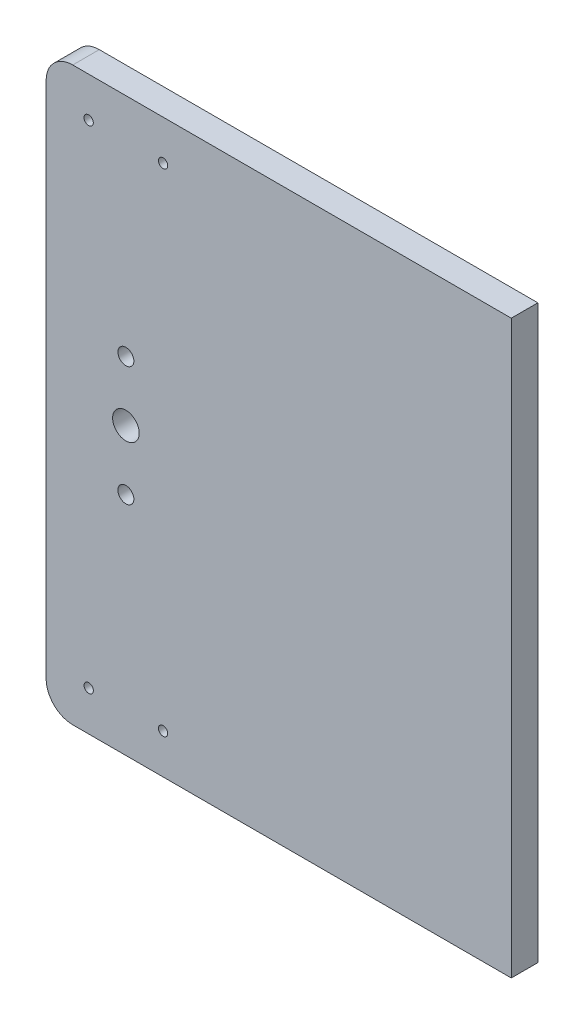
SolidWorks part; units mm, degrees
material "Органическое стекло СО-95-К ГОСТ 10667-90"
ref_plane "Спереди" through (0, 0, 0) normal (0, 0, 1) x (1, 0, 0)
ref_plane "Сверху" through (0, 0, 0) normal (0, 1, 0) x (1, 0, 0)
ref_plane "Справа" through (0, 0, 0) normal (1, 0, 0) x (0, 0, -1)
ref_axis "ОсьX" through (-88.99, 0, 0) along (1, 0, 0)
ref_axis "ОсьZ" through (0, 55, 0) along (0, -1, 0)
ref_axis "ОсьY" through (0, 0, -88.99) along (0, 0, 1)
sketch "Эскиз1" plane through (0, 0, 0) normal (0, 0, 1) x (1, 0, 0)
  line L0 (0, 0) -> (0, 59.9562) construction
  line L1 (-60, 215) -> (290, 215)
  line L3 (-60, -215) -> (290, -215)
  line L4 (290, 215) -> (290, -215)
  line L7 (290, 215) -> (290, -215)
  line L8 (-109.4093, 0) -> (290, 0) construction
  line L9 (-60, 215) -> (-60, -215)
  circle A0 centre (-28, 185) radius 3.5
  circle A16 centre (28, 185) radius 3.5
  circle A17 centre (28, -185) radius 3.5
  circle A18 centre (-28, -185) radius 3.5
  circle A23 centre (0, 0) radius 10
  circle A24 centre (0, 45) radius 6
  circle A25 centre (0, -45) radius 6
  dimension "D3" = 7
  dimension "D4" = 370
  dimension "D5" = 56
  dimension "D6" = 290
  dimension "D8" = 350
  dimension "D11" = 90
  dimension "D12" = 12
  dimension "D13" = 20
  dimension "D2" = 430
extrude "Бобышка-Вытянуть1" add sketch "Эскиз1" along normal blind 20 contours L4 L1 L3 A18 A16 A0 region at (115.533, 0, 0)
fillet "Скругление1" radius 20 2 edges at (-60, 215, 10) (-60, -215, 10)
